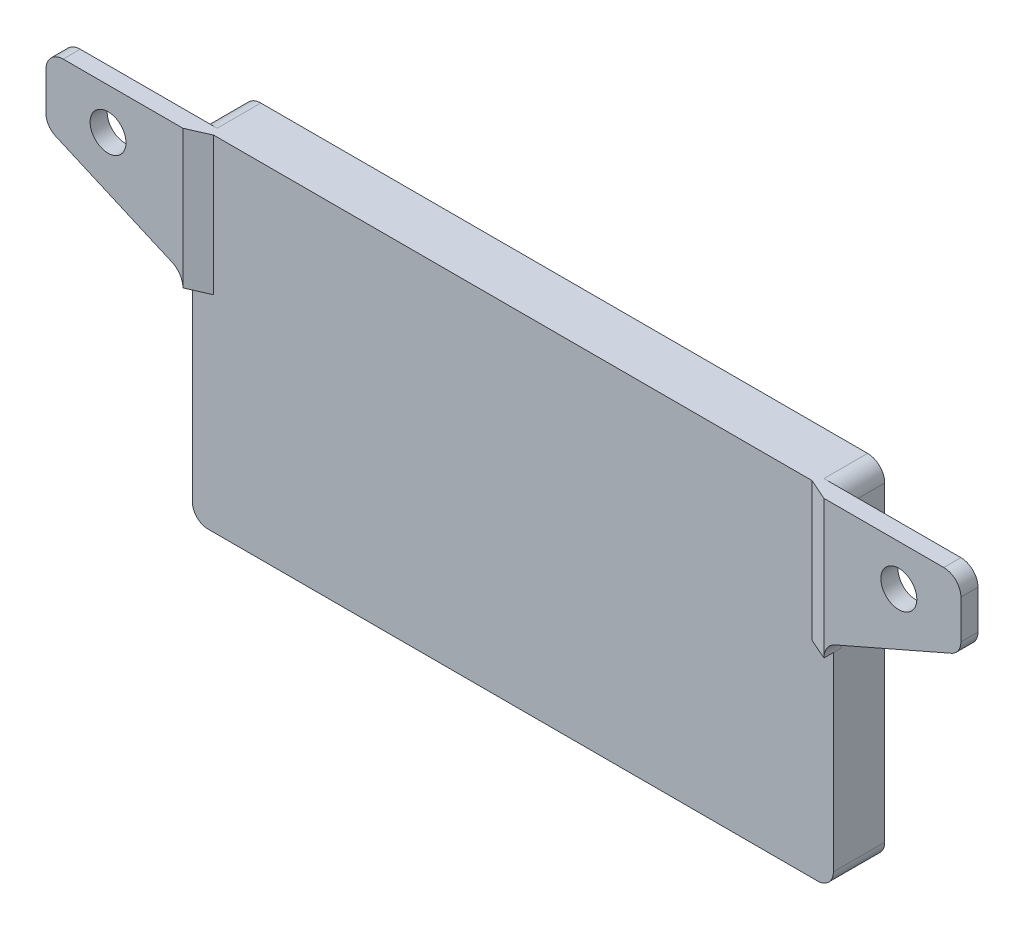
SolidWorks part; units mm, degrees
ref_plane "Front Plane" through (0, 0, 0) normal (0, 0, 1) x (1, 0, 0)
ref_plane "Top Plane" through (0, 0, 0) normal (0, 1, 0) x (1, 0, 0)
ref_plane "Right Plane" through (0, 0, 0) normal (1, 0, 0) x (0, 0, -1)
sketch "Sketch1" plane through (0, 0, 0) normal (0, 0, 1) x (1, 0, 0)
  line L0 (99.95, 149.85) -> (25.05, 149.85)
  line L1 (25.05, 148) -> (25.05, 111.5)
  line L2 (26.9, 109.65) -> (98.1, 109.65)
  line L3 (99.95, 111.5) -> (99.95, 148)
  line L4 (24.9, 148) -> (24.9, 111.5)
  line L5 (26.9, 109.5) -> (98.1, 109.5)
  line L6 (100.1, 111.5) -> (100.1, 148)
  line L7 (102.1, 150) -> (22.9, 150)
  line L8 (24.9, 148) -> (24.9, 111.5) construction
  line L9 (26.9, 109.5) -> (98.1, 109.5) construction
  line L10 (100.1, 111.5) -> (100.1, 148) construction
  line L11 (102.1, 150) -> (22.9, 150) construction
  line L12 (25.05, 148) -> (25.05, 149.85)
  line L14 (101.0046, 149.85) -> (23.9954, 149.85) construction
  line L15 (99.95, 148) -> (99.95, 149.85)
  arc A1 (25.05, 111.5) -> (26.9, 109.65) centre (26.9, 111.5) ccw
  arc A2 (98.1, 109.65) -> (99.95, 111.5) centre (98.1, 111.5) ccw
  arc A4 (24.9, 111.5) -> (26.9, 109.5) centre (26.9, 111.5) ccw
  arc A5 (98.1, 109.5) -> (100.1, 111.5) centre (98.1, 111.5) ccw
  arc A6 (102.1, 150) -> (100.1, 148) centre (102.1, 148) ccw
  arc A7 (24.9, 148) -> (22.9, 150) centre (22.9, 148) ccw
  arc A8 (24.9, 111.5) -> (26.9, 109.5) centre (26.9, 111.5) ccw construction
  arc A9 (98.1, 109.5) -> (100.1, 111.5) centre (98.1, 111.5) ccw construction
  arc A10 (102.1, 150) -> (100.1, 148) centre (102.1, 148) ccw construction
  arc A11 (24.9, 148) -> (22.9, 150) centre (22.9, 148) ccw construction
  arc A16 (25.05, 148) -> (23.9954, 149.85) centre (22.9, 148) ccw construction
  arc A17 (101.0046, 149.85) -> (99.95, 148) centre (102.1, 148) ccw construction
  dimension "D1" = 0
  dimension "D2" = 0.15
extrude "Boss-Extrude1" add sketch "Sketch1" along normal up to surface (5.1 mm away)
sketch "Sketch2" plane through (0, 0, 5.1) normal (0, 0, 1) x (1, 0, 0)
  line L24 (101.2984, 135.5243) -> (114.9016, 141.4757) construction
  line L25 (116.1, 143.308) -> (116.1, 148) construction
  line L26 (118.1, 150) -> (102.1, 150) construction
  line L28 (8.9, 148) -> (8.9, 143.308) construction
  line L29 (10.0984, 141.4757) -> (23.7016, 135.5243) construction
  line L31 (22.9, 150) -> (6.9, 150) construction
  line L32 (101.2984, 135.5243) -> (114.9016, 141.4757) construction
  line L33 (116.1, 143.308) -> (116.1, 148) construction
  line L34 (116.1, 150) -> (102.1, 150) construction
  line L36 (8.9, 148) -> (8.9, 143.308) construction
  line L37 (10.0984, 141.4757) -> (23.7016, 135.5243) construction
  line L39 (22.9, 150) -> (8.9, 150) construction
  line L40 (100.1, 111.5) -> (100.1, 133.692) construction
  line L41 (26.9, 109.5) -> (98.1, 109.5) construction
  line L42 (24.9, 133.692) -> (24.9, 111.5) construction
  line L43 (100.1, 111.5) -> (100.1, 133.692) construction
  line L44 (26.9, 109.5) -> (98.1, 109.5) construction
  line L45 (24.9, 133.692) -> (24.9, 111.5) construction
  line L46 (102.1, 150) -> (22.9, 150) construction
  line L47 (102.1, 150) -> (22.9, 150) construction
  line L48 (8.9, 148) -> (8.9, 150) construction
  line L49 (116.1, 148) -> (116.1, 150) construction
  line L50 (102.1, 149.85) -> (22.9, 149.85)
  line L51 (22.9, 149.85) -> (9.05, 149.85)
  line L52 (9.05, 148) -> (9.05, 149.85)
  line L53 (9.05, 148) -> (9.05, 143.308)
  line L54 (10.1585, 141.6131) -> (23.7618, 135.6617)
  line L55 (25.05, 133.692) -> (25.05, 111.5)
  line L56 (26.9, 109.65) -> (98.1, 109.65)
  line L57 (99.95, 111.5) -> (99.95, 133.692)
  line L58 (101.2382, 135.6617) -> (114.8415, 141.6131)
  line L59 (115.95, 143.308) -> (115.95, 148)
  line L60 (115.95, 148) -> (115.95, 149.85)
  line L61 (115.95, 149.85) -> (102.1, 149.85)
  arc A24 (114.9016, 141.4757) -> (116.1, 143.308) centre (114.1, 143.308) ccw construction
  arc A27 (101.2984, 135.5243) -> (100.1, 133.692) centre (102.1, 133.692) ccw construction
  arc A28 (8.9, 143.308) -> (10.0984, 141.4757) centre (10.9, 143.308) ccw construction
  arc A29 (24.9, 133.692) -> (23.7016, 135.5243) centre (22.9, 133.692) ccw construction
  arc A32 (114.9016, 141.4757) -> (116.1, 143.308) centre (114.1, 143.308) ccw construction
  arc A35 (101.2984, 135.5243) -> (100.1, 133.692) centre (102.1, 133.692) ccw construction
  arc A36 (8.9, 143.308) -> (10.0984, 141.4757) centre (10.9, 143.308) ccw construction
  arc A37 (24.9, 133.692) -> (23.7016, 135.5243) centre (22.9, 133.692) ccw construction
  arc A40 (98.1, 109.5) -> (100.1, 111.5) centre (98.1, 111.5) ccw construction
  arc A41 (24.9, 111.5) -> (26.9, 109.5) centre (26.9, 111.5) ccw construction
  arc A42 (98.1, 109.5) -> (100.1, 111.5) centre (98.1, 111.5) ccw construction
  arc A43 (24.9, 111.5) -> (26.9, 109.5) centre (26.9, 111.5) ccw construction
  arc A44 (9.05, 143.308) -> (10.1585, 141.6131) centre (10.9, 143.308) ccw
  arc A45 (25.05, 133.692) -> (23.7618, 135.6617) centre (22.9, 133.692) ccw
  arc A46 (25.05, 111.5) -> (26.9, 109.65) centre (26.9, 111.5) ccw
  arc A47 (98.1, 109.65) -> (99.95, 111.5) centre (98.1, 111.5) ccw
  arc A48 (101.2382, 135.6617) -> (99.95, 133.692) centre (102.1, 133.692) ccw
  arc A49 (114.8415, 141.6131) -> (115.95, 143.308) centre (114.1, 143.308) ccw
  circle A50 centre (16.3, 145.05) radius 2.1
  circle A51 centre (108.7, 145.05) radius 2.1
  dimension "D2" = 4.2
  dimension "D1" = 0.15
extrude "Boss-Extrude2" add sketch "Sketch2" along normal up to surface (0.9 mm away)
fillet "Fillet1" radius 2 4 edges at (115.95, 149.85, 5.55) (9.05, 149.85, 5.55) (25.05, 149.85, 2.55) (99.95, 149.85, 2.55)
sketch "Sketch3" plane through (0, 0, 6) normal (0, 0, 1) x (1, 0, 0)
  line L0 (99.95, 133.692) -> (99.95, 149.85)
  line L1 (11.05, 149.85) -> (113.95, 149.85) construction
  line L2 (114.8415, 141.6131) -> (101.2382, 135.6617) construction
  line L3 (115.95, 147.85) -> (115.95, 143.308) construction
  line L4 (114.8415, 141.6131) -> (101.2382, 135.6617)
  line L5 (115.95, 147.85) -> (115.95, 143.308)
  line L6 (11.05, 149.85) -> (25.05, 149.85)
  line L7 (25.05, 133.692) -> (25.05, 149.85)
  line L8 (23.7618, 135.6617) -> (10.1585, 141.6131) construction
  line L9 (9.05, 143.308) -> (9.05, 147.85) construction
  line L10 (23.7618, 135.6617) -> (10.1585, 141.6131)
  line L11 (9.05, 143.308) -> (9.05, 147.85)
  line L12 (99.95, 149.85) -> (113.95, 149.85)
  arc A0 (101.2382, 135.6617) -> (99.95, 133.692) centre (102.1, 133.692) ccw construction
  arc A1 (114.8415, 141.6131) -> (115.95, 143.308) centre (114.1, 143.308) ccw construction
  arc A2 (115.95, 147.85) -> (113.95, 149.85) centre (113.95, 147.85) ccw construction
  arc A3 (101.2382, 135.6617) -> (99.95, 133.692) centre (102.1, 133.692) ccw
  arc A4 (114.8415, 141.6131) -> (115.95, 143.308) centre (114.1, 143.308) ccw
  arc A5 (115.95, 147.85) -> (113.95, 149.85) centre (113.95, 147.85) ccw
  arc A6 (25.05, 133.692) -> (23.7618, 135.6617) centre (22.9, 133.692) ccw construction
  arc A7 (9.05, 143.308) -> (10.1585, 141.6131) centre (10.9, 143.308) ccw construction
  arc A8 (11.05, 149.85) -> (9.05, 147.85) centre (11.05, 147.85) ccw construction
  arc A9 (25.05, 133.692) -> (23.7618, 135.6617) centre (22.9, 133.692) ccw
  arc A10 (9.05, 143.308) -> (10.1585, 141.6131) centre (10.9, 143.308) ccw
  arc A11 (11.05, 149.85) -> (9.05, 147.85) centre (11.05, 147.85) ccw
  circle A12 centre (108.7, 145.05) radius 2.1 construction
  circle A13 centre (16.3, 145.05) radius 2.1 construction
  circle A14 centre (108.7, 145.05) radius 2.1
  circle A15 centre (16.3, 145.05) radius 2.1
extrude "Boss-Extrude3" add sketch "Sketch3" along normal offset from surface (1.1 mm away) 2 up to face at (17.4291, 143.8163, 5.1)
sketch "Sketch4" plane through (0, 149.85, 0) normal (0, 1, 0) x (1, 0, 0)
  line L0 (99.95, -7.1) -> (97.45, -6)
  line L1 (25.05, -6) -> (99.95, -6) construction
  line L2 (97.45, -6) -> (99.95, -6)
  line L3 (25.05, -6) -> (25.05, -7.1)
  line L4 (25.05, -7.1) -> (27.55, -6)
  line L5 (27.55, -6) -> (25.05, -6)
  line M6 (25.05, -7.1) -> (25.05, -6)
  line M7 (25.05, -6) -> (99.95, -6)
  line M8 (99.95, -6) -> (99.95, -7.1)
  dimension "D1" = 2.5
extrude "Boss-Extrude4" add sketch "Sketch4" against normal up to vertex (16.158 mm away) contours L4 M6 M7 | L0 M8 M7 region at (25.8833, 149.85, 6.3667) region at (99.1167, 149.85, 6.3667) up to point (25.05, 133.692, 7.1)
equation "\"width\"= 24"
equation "\"thk\"= 3"
equation "\"holesize\"= 4.2"
equation "\"holedistance\"= ( 20 + 12 ) / 2"
equation "\"threaded_hole\"= 3.9"
equation "\"fillet_radius\"= 2"
equation "\"ground_clearance\"= 25"
equation "\"tire_thk\"= 3"
equation "\"innerwheel_diam\" = \"wheel_diam\"-2*\"tire_thk\""
equation "\"innerwheel_thk\"= 8"
equation "\"wheel_diam\"= 2*(\"width\"/2+\"ground_clearance\")"
equation "\"coloursensor_holesize\"= 2.65"
equation "\"hole_to_edge\" = 4"
equation "\"M4_insert_diam\"= 5.7"
